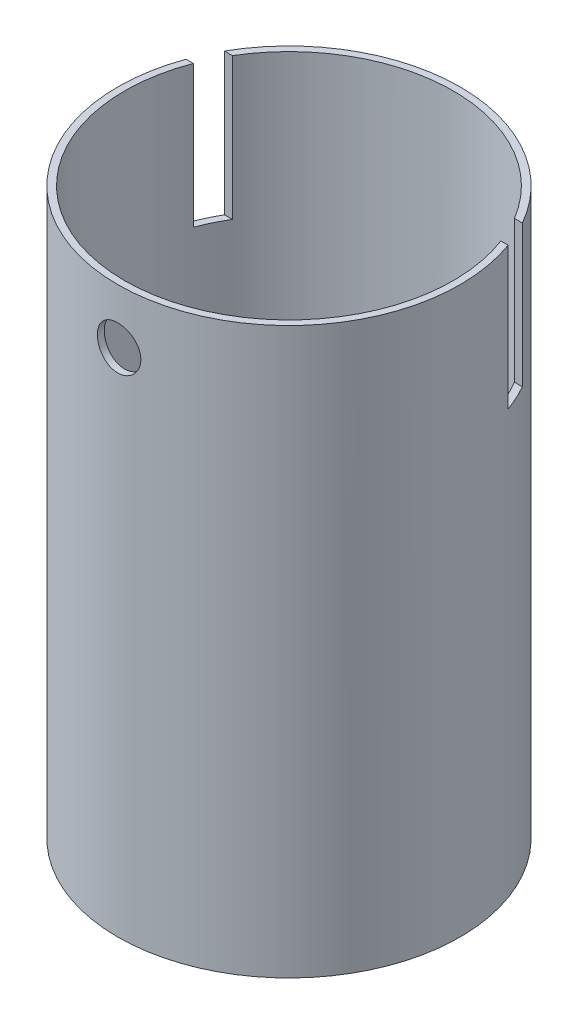
SolidWorks part; units mm, degrees
ref_plane "Front Plane" through (0, 0, 0) normal (0, 0, 1) x (1, 0, 0)
ref_plane "Top Plane" through (0, 0, 0) normal (0, 1, 0) x (1, 0, 0)
ref_plane "Right Plane" through (0, 0, 0) normal (1, 0, 0) x (0, 0, -1)
sketch "Sketch2" plane through (0, 0, 0) normal (0, 1, 0) x (1, 0, 0)
  circle A0 centre (0, 0) radius 50
  dimension "D1" = 100
extrude "Boss-Extrude1" add sketch "Sketch2" along normal blind 165
sketch "Sketch3" plane through (0, 165, 0) normal (0, 1, 0) x (1, 0, 0)
  circle A0 centre (0, 0) radius 48
  circle A1 centre (0, 0) radius 50 construction
  dimension "D1" = 2
extrude "Cut-Extrude1" cut sketch "Sketch3" along direction (0, 1, 0) on the side against the normal offset from surface (163 mm away) 2 up to face at (0, 0, 50)
sketch "Sketch4" plane through (0, 0, 0) normal (0, -1, 0) x (1, 0, 0)
  line L2 (-12.9854, -35.1642) -> (-12.9854, -29.1642)
  line L3 (-12.9854, -29.1642) -> (11.4146, -29.1642)
  line L4 (11.4146, -35.1642) -> (11.4146, -29.1642)
  line L14 (-12.9854, -35.1642) -> (11.4146, -35.1642)
  circle A0 centre (0, 0) radius 50 construction
  circle A1 centre (0, 0) radius 50 construction
  dimension "D1" = 24.4
  dimension "D2" = 6
  dimension "D3" = 29.1642
  dimension "D4" = 12.9854
extrude "Cut-Extrude2" cut sketch "Sketch4" against normal up to surface (2 mm away) up to face at (0, 2, 48)
sketch "Sketch5" plane through (0, 2, 0) normal (0, 1, 0) x (1, 0, 0)
  line L0 (11.4146, 35.1642) -> (11.4146, 29.1642) construction
  line L1 (11.4146, 29.1642) -> (-12.9854, 29.1642) construction
  line L2 (-12.9854, 29.1642) -> (-12.9854, 35.1642) construction
  line L3 (11.4146, 35.1642) -> (11.4146, 29.1642)
  line L4 (11.4146, 29.1642) -> (-12.9854, 29.1642)
  line L5 (-12.9854, 29.1642) -> (-12.9854, 35.1642)
  line L7 (-14.9854, 37.1642) -> (-14.9854, 27.1642)
  line L8 (-14.9854, 27.1642) -> (13.4146, 27.1642)
  line L9 (13.4146, 27.1642) -> (13.4146, 37.1642)
  line L15 (-14.9854, 37.1642) -> (13.4146, 37.1642)
  line L16 (-12.9854, 35.1642) -> (11.4146, 35.1642) construction
  line M13 (11.4146, 35.1642) -> (11.4146, 29.1642)
  line M14 (11.4146, 29.1642) -> (-12.9854, 29.1642)
  line M15 (-12.9854, 29.1642) -> (-12.9854, 35.1642)
  line M20 (-12.9854, 35.1642) -> (11.4146, 35.1642)
  dimension "D1" = 2
  dimension "D3" = 2
  dimension "D4" = 2
  dimension "D5" = 2
extrude "Boss-Extrude2" add sketch "Sketch5" along normal blind 36 contours L15 L7 L8 L9 M13 M14 M15 M20 region at (-0.7854, 2, -36.8631)
sketch "Sketch6" plane through (0, 38, 0) normal (0, 1, 0) x (1, 0, 0)
  line L6 (-14.9854, 27.1642) -> (13.4146, 27.1642) construction
  line L7 (-12.9854, 29.1642) -> (11.4146, 29.1642)
  line L8 (-12.9854, 29.1642) -> (-12.9854, 27.1642)
  line L9 (-12.9854, 27.1642) -> (11.4146, 27.1642)
  line L10 (11.4146, 29.1642) -> (11.4146, 27.1642)
  line L11 (11.4146, 35.1642) -> (11.4146, 29.1642) construction
  line L12 (-14.9854, 37.1642) -> (13.4146, 37.1642) construction
  line L13 (-12.9854, 35.1642) -> (11.4146, 35.1642)
  line L14 (-12.9854, 35.1642) -> (-12.9854, 37.1642)
  line L15 (-12.9854, 37.1642) -> (11.4146, 37.1642)
  line L16 (11.4146, 35.1642) -> (11.4146, 37.1642)
  line M22 (-14.9854, 27.1642) -> (13.4146, 27.1642)
  line M25 (11.4146, 29.1642) -> (-12.9854, 29.1642)
extrude "Cut-Extrude3" cut sketch "Sketch6" against normal blind 8 contours L10 L8 M25 M22 region at (-0.7854, 38, -28.1642)
extrude "Cut-Extrude4" cut sketch "Sketch6<4>" against normal blind 30 contours L15 L16 L13 L14
sketch "Sketch6<4>" plane through (0, 38, 0) normal (0, 1, 0) x (1, 0, 0) same geometry as "Sketch6"
sketch "Sketch7" plane through (0, 2, 0) normal (0, 1, 0) x (1, 0, 0)
  line L0 (0, 48) -> (0, -48) construction
  line L1 (-30.4, 18.2) -> (-24.4, 18.2)
  line L2 (-30.4, 18.2) -> (-30.4, 12.2)
  line L3 (-30.4, -27) -> (-24.4, -27)
  line L4 (-4, 18.2) -> (-4, 12.2)
  line L5 (-48, 0) -> (48, 0) construction
  line L6 (-32.4, 20.2) -> (-32.4, 12.2)
  line L7 (-32.4, -29) -> (-24.4, -29)
  line L8 (-2, 20.2) -> (-2, 12.2)
  line L9 (-32.4, 20.2) -> (-24.4, 20.2)
  line L10 (-32.4, 12.2) -> (-30.4, 12.2)
  line L11 (-32.4, -21) -> (-30.4, -21)
  line L12 (-24.4, 20.2) -> (-24.4, 18.2)
  line L13 (-10, 20.2) -> (-10, 18.2)
  line L14 (-32.4, -21) -> (-32.4, -29)
  line L15 (-32.4, 20.2) -> (-32.4, -29) construction
  line L16 (-30.4, -21) -> (-30.4, -27)
  line L17 (-30.4, 18.2) -> (-30.4, -27) construction
  line L18 (-24.4, -27) -> (-24.4, -29)
  line L19 (-10, -27) -> (-10, -29)
  line L20 (-4, -21) -> (-4, -27)
  line L21 (-4, 18.2) -> (-4, -27) construction
  line L22 (-2, -21) -> (-2, -29)
  line L23 (-2, 20.2) -> (-2, -29) construction
  line L24 (-4, 12.2) -> (-2, 12.2)
  line L25 (-10, 20.2) -> (-2, 20.2)
  line L26 (-32.4, 20.2) -> (-2, 20.2) construction
  line L27 (-10, 18.2) -> (-4, 18.2)
  line L28 (-30.4, 18.2) -> (-4, 18.2) construction
  line L29 (-4, -21) -> (-2, -21)
  line L30 (-10, -27) -> (-4, -27)
  line L31 (-30.4, -27) -> (-4, -27) construction
  line L32 (-10, -29) -> (-2, -29)
  line L33 (-32.4, -29) -> (-2, -29) construction
  circle A0 centre (0, 0) radius 48 construction
  circle A1 centre (0, 0) radius 48 construction
  dimension "D1" = 26.4
  dimension "D2" = 45.2
  dimension "D3" = 4
  dimension "D4" = 27
  dimension "D6" = 8
  dimension "D7" = 8
  dimension "D8" = 8
  dimension "D9" = 8
  dimension "D5" = 2
extrude "Boss-Extrude3" add sketch "Sketch7" along normal blind 3
fillet "Fillet1" radius 0.5 24 edges at (-27.4, 5, 27) (-24.4, 5, 28) (-28.4, 5, 29) (-32.4, 5, 25) (-31.4, 5, 21) (-30.4, 5, 24) (-4, 5, 24) (-3, 5, 21) (-2, 5, 25) (-6, 5, 29) (-10, 5, 28) (-7, 5, 27) (-10, 5, -19.2) (-6, 5, -20.2) (-2, 5, -16.2) (-3, 5, -12.2) (-4, 5, -15.2) (-7, 5, -18.2) (-31.4, 5, -12.2) (-32.4, 5, -16.2) (-28.4, 5, -20.2) (-24.4, 5, -19.2) (-27.4, 5, -18.2) (-30.4, 5, -15.2)
mirror "Mirror1" about plane through (0, 0, 0) normal (1, 0, 0) of "Fillet1", "Boss-Extrude3"
sketch "Sketch8" plane through (0, 2, 0) normal (0, 1, 0) x (1, 0, 0)
  line L0 (-48, 0) -> (48, 0) construction
  line L1 (-41.9, 8.89) -> (-37.9, 8.89)
  line L2 (-41.9, 8.89) -> (-41.9, -8.89)
  line L3 (-41.9, -8.89) -> (-37.9, -8.89)
  line L4 (-37.9, 8.89) -> (-37.9, -8.89)
  line L5 (-32.4, 20.2) -> (-32.4, 12.2) construction
  point P4 (-41.9, 0)
  dimension "D1" = 4
  dimension "D2" = 17.78
  dimension "D3" = 5.5
extrude "Boss-Extrude4" add sketch "Sketch8" along normal blind 6
fillet "Fillet2" radius 3 2 edges at (-39.9, 8, 8.89) (-39.9, 8, -8.89)
sketch "Sketch10" plane through (-37.9, 0, 0) normal (1, 0, 0) x (0, 0, -1)
  line L0 (48, 2) -> (-48, 2) construction
  line L1 (-4.064, 2) -> (4.064, 2)
  line L2 (-4.064, 2) -> (-4.064, 4.54)
  line L3 (-4.064, 4.54) -> (4.064, 4.54)
  line L4 (4.064, 2) -> (4.064, 4.54)
  line L5 (0, 8) -> (0, 12.0582) construction
  line L6 (-5.89, 8) -> (5.89, 8) construction
  point P11 (0, 4.54)
  dimension "D1" = 8.128
  dimension "D2" = 2.54
extrude "Cut-Extrude5" cut sketch "Sketch10" against normal up to surface (4 mm away) up to face at (-41.9, 5.2071, 0)
mirror "Mirror3" about plane through (0, 0, 0) normal (1, 0, 0) of "Cut-Extrude5", "Fillet2", "Boss-Extrude4"
sketch "Sketch11" plane through (-60.082, 96.7311, 38.1369) normal (0, 0, 1) x (1, 0, 0)
  line L1 (71.4621, 10.6574) -> (67.4621, 10.6574)
  line L2 (71.4621, 10.6574) -> (71.4621, 4.6574)
  line L3 (71.4621, 4.6574) -> (67.4621, 4.6574)
  line L4 (67.4621, 10.6574) -> (67.4621, 4.6574)
  line L5 (43.2921, 10.6574) -> (39.2921, 10.6574)
  line L6 (43.2921, 10.6574) -> (43.2921, 4.6574)
  line L7 (43.2921, 4.6574) -> (39.2921, 4.6574)
  line L8 (39.2921, 10.6574) -> (39.2921, 4.6574)
  circle A2 centre (69.4621, 8.6007) radius 1.6 construction
  circle A3 centre (41.2921, 8.6007) radius 1.6 construction
  dimension "D5" = 0.4
  dimension "D6" = 0.4
  dimension "D1" = 4
  dimension "D2" = 6
  dimension "D3" = 4
extrude "Boss-Extrude5" add sketch "Sketch11" along normal up to next
sketch "Sketch12" plane through (0, 0, 38.1369) normal (0, 0, -1) x (-1, 0, 0)
  arc A0 (18.8423, 106.8309) -> (19.8776, 106.3648) centre (18.7899, 105.3318) ccw construction
  arc A1 (18.8423, 106.8309) -> (19.8776, 106.3648) centre (18.7899, 105.3318) ccw construction
sketch "Sketch13" plane through (0, 0, 38.1369) normal (0, 0, -1) x (-1, 0, 0)
  arc A0 (-9.3277, 106.8309) -> (-8.2924, 106.3648) centre (-9.3801, 105.3318) ccw construction
  arc A1 (-9.3277, 106.8309) -> (-8.2924, 106.3648) centre (-9.3801, 105.3318) ccw construction
sketch "Sketch14" plane through (0, 0, 38.1369) normal (0, 0, -1) x (-1, 0, 0)
  circle A0 centre (-9.3801, 105.3318) radius 1.5
  circle A1 centre (18.7899, 105.3318) radius 1.5
extrude "Cut-Extrude6" cut sketch "Sketch14" against normal blind 4.5
sketch "Sketch15" plane through (0, 165, 0) normal (0, 1, 0) x (1, 0, 0)
  line L1 (-55, 24.6642) -> (55, 24.6642)
  line L7 (0, 48) -> (0, 0) construction
  line L12 (-55, 16.9771) -> (55, 16.9771)
  line L13 (55, 16.9771) -> (55, 24.6642)
  line L14 (-55, 16.9771) -> (-55, 24.6642)
  point P4 (0, 16.9771)
  dimension "D1" = 110
extrude "Cut-Extrude7" cut sketch "Sketch15" against normal blind 41.42
ref_plane "Plane2" through (40, 0, 0) normal (1, 0, 0) x (0, 0, -1)
sketch "Sketch17" plane through (40, 0, 0) normal (1, 0, 0) x (0, 0, -1)
  line L1 (47.5595, 38.4544) -> (14.5595, 38.4544)
  line L3 (47.5595, 43.4544) -> (13.494, 43.4544)
  line L5 (13.494, 43.4544) -> (13.494, 40.714)
  line L6 (13.494, 40.714) -> (-0.3763, 40.714)
  line L7 (-0.3763, 40.714) -> (-0.3763, 43.4544)
  line L10 (-0.3763, 43.4544) -> (14.5595, 43.4544)
  line L11 (14.5595, 39.7648) -> (14.5595, 92.8648) construction
  line L12 (11.9348, 54.9321) -> (11.9348, 70.5475) construction
  line L13 (10.9348, 54.9321) -> (10.9348, 70.5475)
  line L14 (12.9348, 54.9321) -> (12.9348, 70.5475)
  line L15 (14.5595, 43.4544) -> (14.5595, 38.4544)
  line L16 (47.5595, 38.4544) -> (47.5595, 43.4544)
  arc A1 (10.9348, 54.9321) -> (12.9348, 54.9321) centre (11.9348, 54.9321) ccw
  arc A2 (12.9348, 70.5475) -> (10.9348, 70.5475) centre (11.9348, 70.5475) ccw
  circle A3 centre (-16.0592, 68.8572) radius 1
  point P12 (11.9348, 62.7398)
  dimension "D3" = 1
  dimension "D4" = 2
  dimension "D1" = 33
  dimension "D2" = 5
ref_plane "Plane3" through (0, 0, 50) normal (0, 0, 1) x (1, 0, 0)
sketch "Sketch18" plane through (0, 0, 50) normal (0, 0, 1) x (1, 0, 0)
  line L0 (50, 165) -> (-50, 165) construction
  line L3 (-50, 165) -> (50, 165) construction
  circle A0 centre (0, 149) radius 6.35
  point P3 (0, 165)
  dimension "D1" = 12.7
  dimension "D2" = 16
extrude "Cut-Extrude9" cut sketch "Sketch18" against normal blind 8
chamfer "Chamfer1" distance 5 angle 75 2 edges at (-13.9854, 38, -37.1642) (12.4146, 38, -37.1642) first distance on face at (-13.9854, 38, -32.1642) first distance on face at (12.4146, 38, -32.1642)
